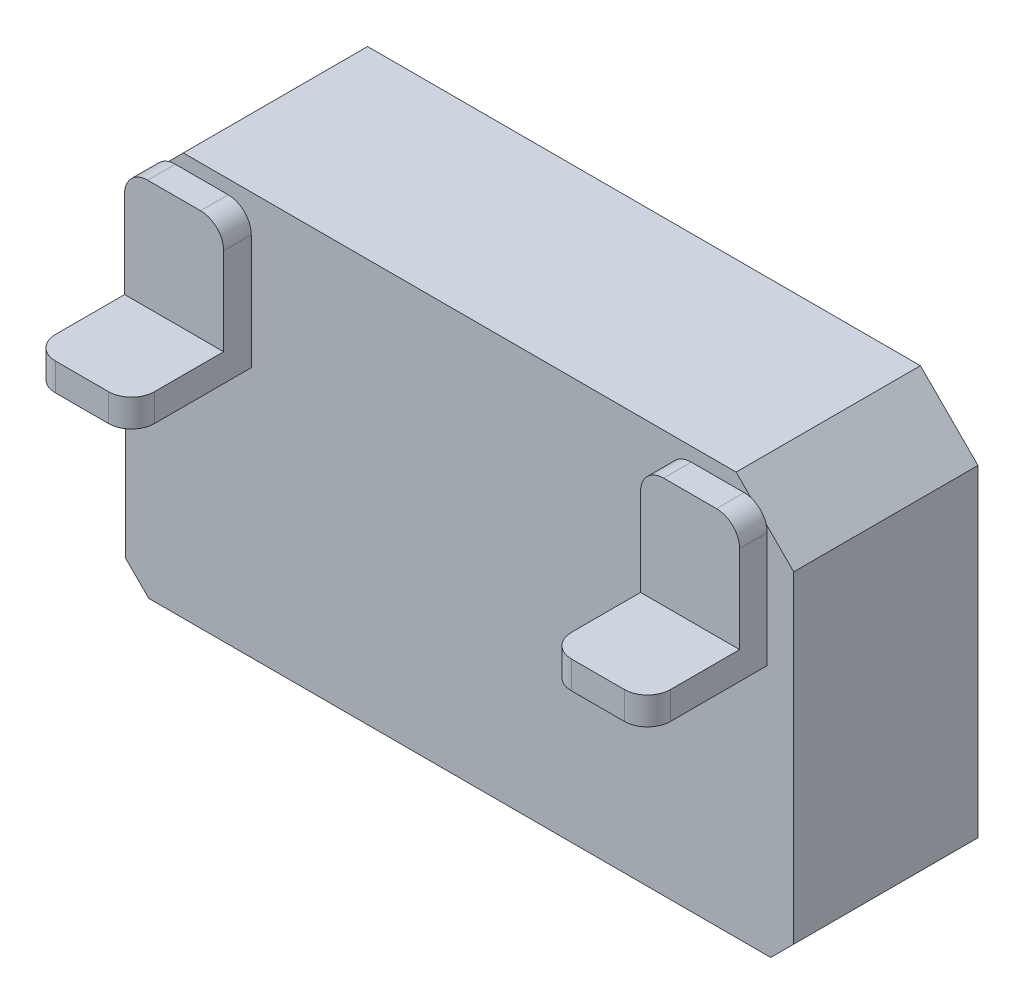
SolidWorks part; units mm, degrees
ref_plane "前视基准面" through (0, 0, 0) normal (0, 0, 1) x (1, 0, 0)
ref_plane "上视基准面" through (0, 0, 0) normal (0, 1, 0) x (1, 0, 0)
ref_plane "右视基准面" through (0, 0, 0) normal (1, 0, 0) x (0, 0, -1)
sketch "草图1" plane through (0, 0, 0) normal (0, 0, 1) x (1, 0, 0)
  line L0 (-145, -77.5) -> (-135, -87.5)
  line L1 (-120, 87.5) -> (120, 87.5)
  line L2 (-145, 62.5) -> (-145, -77.5)
  line L3 (-135, -87.5) -> (135, -87.5)
  line L4 (145, 62.5) -> (145, -77.5)
  line L5 (-145, 87.5) -> (145, -87.5) construction
  line L6 (-145, -87.5) -> (145, 87.5) construction
  line L7 (135, -87.5) -> (145, -77.5)
  line L8 (-145, 62.5) -> (-120, 87.5)
  line L9 (120, 87.5) -> (145, 62.5)
  point P0 (0, 0)
  dimension "D1" = 175
  dimension "D2" = 290
extrude "凸台-拉伸1" add sketch "草图1" along normal blind 80
sketch "草图2" plane through (0, 0, 80) normal (0, 0, 1) x (1, 0, 0)
  line L0 (-133.5, 81.5) -> (-133.5, 21.5)
  line L1 (120, 87.5) -> (-120, 87.5) construction
  line L2 (-133.5, 21.5) -> (-90.5, 21.5)
  line L3 (-90.5, 21.5) -> (-90.5, 81.5)
  line L4 (0, 87.5) -> (0, -87.5) construction
  line L5 (-135, -87.5) -> (135, -87.5) construction
  line L6 (-133.5, 81.5) -> (-90.5, 81.5)
  line L7 (133.5, 81.5) -> (133.5, 21.5)
  line L8 (133.5, 21.5) -> (90.5, 21.5)
  line L9 (90.5, 21.5) -> (90.5, 81.5)
  line L10 (133.5, 81.5) -> (90.5, 81.5)
  point P14 (-112, 81.5)
  point P15 (112, 81.5)
  dimension "D1" = 224
  dimension "D2" = 43
  dimension "D3" = 60
  dimension "D4" = 6
extrude "凸台-拉伸2" add sketch "草图2" along normal blind 12
sketch "草图3" plane through (0, 0, 92) normal (0, 0, 1) x (1, 0, 0)
  line L0 (-90.5, 21.5) -> (-90.5, 81.5) construction
  line L1 (-133.5, 21.5) -> (-90.5, 21.5)
  line L2 (-133.5, 21.5) -> (-133.5, 33.5)
  line L3 (-133.5, 33.5) -> (-90.5, 33.5)
  line L4 (-90.5, 21.5) -> (-90.5, 33.5)
  line L5 (-112, 33.5) -> (-112, 21.5) construction
  line L6 (-133.5, 27.5) -> (-90.5, 27.5) construction
  line L7 (133.5, 21.5) -> (133.5, 74) construction
  line L8 (90.5, 21.5) -> (133.5, 21.5)
  line L9 (90.5, 21.5) -> (90.5, 33.5)
  line L10 (90.5, 33.5) -> (133.5, 33.5)
  line L11 (133.5, 21.5) -> (133.5, 33.5)
  line L12 (112, 33.5) -> (112, 21.5) construction
  line L13 (90.5, 27.5) -> (133.5, 27.5) construction
  point P158 (112, 27.5)
  point P184 (-112, 27.5)
  dimension "D1" = 12
extrude "凸台-拉伸3" add sketch "草图3" along normal blind 40
fillet "圆角1" radius 10 8 edges at (-133.5, 81.5, 86) (-133.5, 27.5, 132) (-90.5, 27.5, 132) (90.5, 27.5, 132) (133.5, 27.5, 132) (-90.5, 81.5, 86) (133.5, 81.5, 86) (90.5, 81.5, 86)
